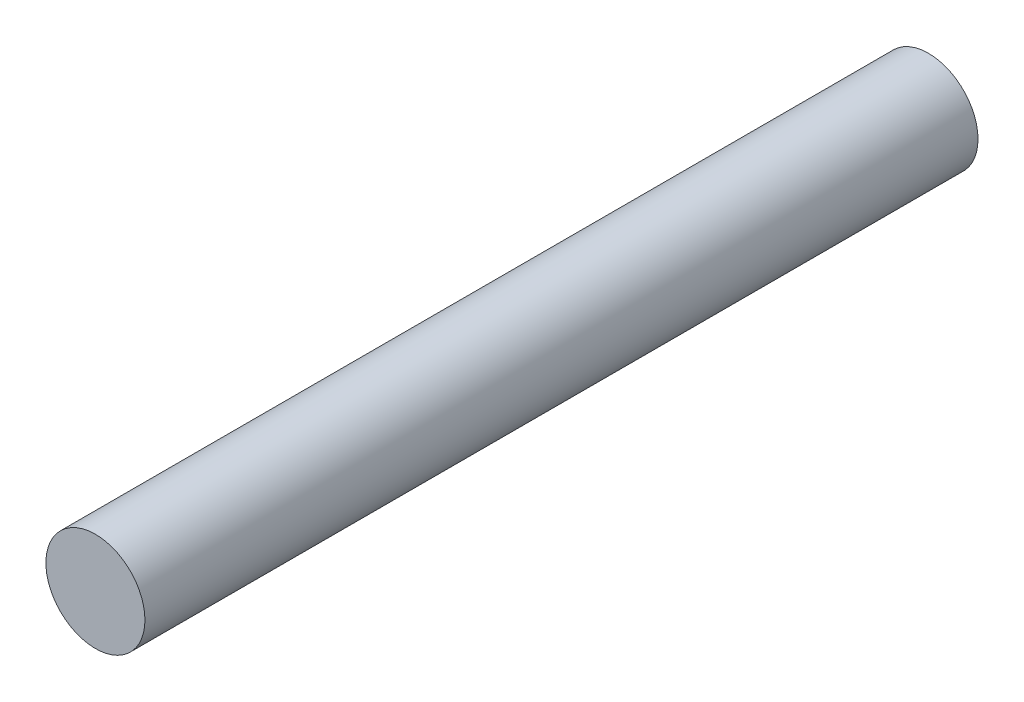
SolidWorks part; units mm, degrees
ref_plane "Front Plane" through (0, 0, 0) normal (0, 0, 1) x (1, 0, 0)
ref_plane "Top Plane" through (0, 0, 0) normal (0, 1, 0) x (1, 0, 0)
ref_plane "Right Plane" through (0, 0, 0) normal (1, 0, 0) x (0, 0, -1)
sketch "Sketch2" plane through (0, 0, 0) normal (0, 1, 0) x (1, 0, 0)
  line L0 (0, 0) -> (0, -67.3)
  line L1 (0, 0) -> (4, 0)
  line L2 (0, -25.9144) -> (0, 43.7641) construction
  line L3 (4, 0) -> (4, -67.3)
  line L4 (4, -67.3) -> (0, -67.3)
  point P5 (4, 23.3358)
  point P8 (0, 0)
  dimension "D1" = 67.3
  dimension "D2" = 8
revolve "Revolve1" add sketch "Sketch2" angle 360 about L2
